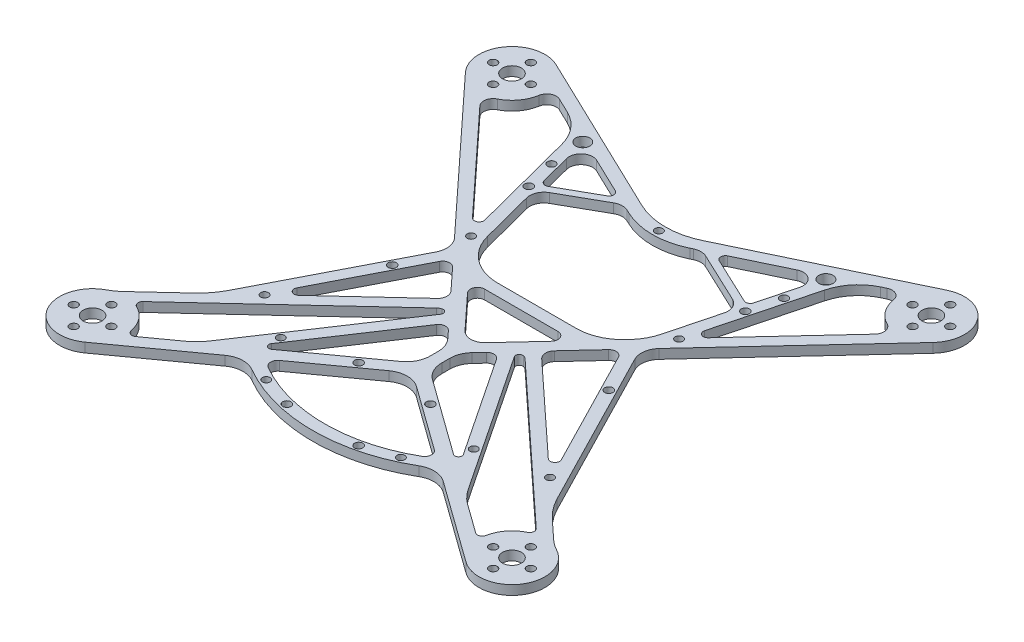
SolidWorks part; units mm, degrees
material "Thornel Mat VMA"
ref_plane "前视基准面" through (0, 0, 0) normal (0, 0, 1) x (1, 0, 0)
ref_plane "上视基准面" through (0, 0, 0) normal (0, 1, 0) x (1, 0, 0)
ref_plane "右视基准面" through (0, 0, 0) normal (1, 0, 0) x (0, 0, -1)
sketch "草图1" plane through (0, 0, 0) normal (0, 1, 0) x (1, 0, 0)
  line L0 (0, 0) -> (89.0955, 89.0955) construction
  line L1 (0, 0) -> (126, 0) construction
  line L2 (0, 0) -> (0, 126) construction
  line L3 (89.0955, 154.5955) -> (-89.0955, 154.5955)
  line L4 (154.5955, -89.0955) -> (154.5955, 89.0955)
  line L5 (-89.0955, -154.5955) -> (89.0955, -154.5955)
  line L6 (-154.5955, 89.0955) -> (-154.5955, -89.0955)
  line L7 (89.0955, 89.0955) -> (81.0955, 89.0955) construction
  circle A0 centre (0, 0) radius 126
  circle A1 centre (89.0955, 89.0955) radius 65.5
  circle A2 centre (89.0955, -89.0955) radius 65.5
  circle A3 centre (-89.0955, -89.0955) radius 65.5
  circle A4 centre (-89.0955, 89.0955) radius 65.5
  circle A5 centre (89.0955, 89.0955) radius 8 construction
  circle A6 centre (81.0955, 89.0955) radius 1.7
  circle A7 centre (89.0955, 97.0955) radius 1.7
  circle A8 centre (97.0955, 89.0955) radius 1.7
  circle A9 centre (89.0955, 81.0955) radius 1.7
  circle A10 centre (97.0955, -89.0955) radius 1.7
  circle A11 centre (89.0955, -89.0955) radius 8 construction
  circle A12 centre (89.0955, -97.0955) radius 1.7
  circle A13 centre (81.0955, -89.0955) radius 1.7
  circle A14 centre (89.0955, -81.0955) radius 1.7
  circle A15 centre (-89.0955, -97.0955) radius 1.7
  circle A16 centre (-89.0955, -89.0955) radius 8 construction
  circle A17 centre (-97.0955, -89.0955) radius 1.7
  circle A18 centre (-89.0955, -81.0955) radius 1.7
  circle A19 centre (-81.0955, -89.0955) radius 1.7
  circle A20 centre (-97.0955, 89.0955) radius 1.7
  circle A21 centre (-89.0955, 89.0955) radius 8 construction
  circle A22 centre (-89.0955, 97.0955) radius 1.7
  circle A23 centre (-81.0955, 89.0955) radius 1.7
  circle A24 centre (-89.0955, 81.0955) radius 1.7
  circle A25 centre (89.0955, 89.0955) radius 4
  circle A26 centre (89.0955, -89.0955) radius 4
  circle A27 centre (-89.0955, -89.0955) radius 4
  circle A28 centre (-89.0955, 89.0955) radius 4
  point P16 (0, 0)
  point P24 (0, 0)
  point P35 (89.0955, 89.0955)
  point P66 (0, 0)
  point P74 (0, 0)
  dimension "D1" = 252
  dimension "D3" = 131
  dimension "D6" = 3.4
  dimension "D7" = 16
  dimension "D10" = 8
  dimension "D2" = 45
  dimension "D4" = 4
  dimension "D5" = 4
  dimension "D8" = 4
  dimension "D9" = 4
  dimension "D11" = 4
extrude "凸台-拉伸1" add sketch "草图1" along normal blind 4 contours A4 A0 A3 A2 A1 | A0 A1 A9 A6 | A0 A1 A8 A7 | A2 L4 A1 A0 | A0 A2 A14 A13 | A2 A0 A12 A10 | A3 L5 A2 A0 | A0 A3 A19 A18 | A3 A0 A17 A15 | A4 L6 A3 A0 | A0 A4 A22 A20 | A0 A4 A24 A23 | A4 A0 A1 L3 region at (0, 0, -141.657) region at (106.5116, 0, -106.5116) region at (-106.5116, 0, -106.5116) region at (141.657, 0, 0) region at (0, 0, 0) region at (67.2963, 0, -67.2963) region at (-141.657, 0, 0) region at (-67.2963, 0, -67.2963) region at (106.5116, 0, 106.5116) region at (-106.5116, 0, 106.5116) region at (0, 0, 141.657) region at (67.2963, 0, 67.2963) region at (-67.2963, 0, 67.2963)
sketch "草图2" plane through (0, 4, 0) normal (0, 1, 0) x (1, 0, 0)
  circle A0 centre (-89.0955, 89.0955) radius 72
  circle A1 centre (-89.0955, 89.0955) radius 74
  circle A2 centre (89.0955, 89.0955) radius 74
  circle A3 centre (89.0955, 89.0955) radius 72
  circle A4 centre (89.0955, -89.0955) radius 74
  circle A5 centre (89.0955, -89.0955) radius 72
  circle A6 centre (-89.0955, -89.0955) radius 74
  circle A7 centre (-89.0955, -89.0955) radius 72
  point P20 (0, 0)
  dimension "D1" = 144
  dimension "D2" = 2
  dimension "D3" = 4
extrude "凸台-拉伸2" [suppressed] add sketch "草图2" along normal blind 25 separate body
sketch "草图5" plane through (0, 0, 0) normal (0, -1, 0) x (1, 0, 0)
  line L1 (-15.25, -15.25) -> (15.25, -15.25) construction
  line L2 (-15.25, -15.25) -> (-15.25, 15.25) construction
  line L3 (-15.25, 15.25) -> (15.25, 15.25) construction
  line L4 (15.25, -15.25) -> (15.25, 15.25) construction
  line L5 (-15.25, -15.25) -> (15.25, 15.25) construction
  line L6 (-15.25, 15.25) -> (15.25, -15.25) construction
  circle A0 centre (15.25, 15.25) radius 1.75
  circle A1 centre (-15.25, 15.25) radius 1.75
  circle A2 centre (-15.25, -15.25) radius 1.75
  circle A3 centre (15.25, -15.25) radius 1.75
  point P0 (0, 0)
  dimension "D2" = 3.5
  dimension "D1" = 30.5
extrude "切除-拉伸2" [suppressed] cut sketch "草图5" against normal through all
sketch "草图3" plane through (0, 0, 0) normal (0, -1, 0) x (1, 0, 0)
  line L0 (-78.4912, 99.7044) -> (0, 21.2485)
  line L1 (-89.0955, -89.0955) -> (89.0955, -89.0955) construction
  line L2 (-89.0955, -89.0955) -> (-89.0955, 89.0955) construction
  line L7 (-89.0955, 89.0955) -> (89.0955, 89.0955) construction
  line L8 (89.0955, -89.0955) -> (89.0955, 89.0955) construction
  line L9 (-89.0955, -89.0955) -> (89.0955, 89.0955) construction
  line L10 (-89.0955, 89.0955) -> (89.0955, -89.0955) construction
  line L11 (0, 21.2485) -> (78.4912, 99.7044)
  line L12 (0, 0) -> (0, 165.7353) construction
  line L13 (21.2485, 0) -> (99.7044, -78.4912)
  line L14 (99.7044, 78.4912) -> (21.2485, 0)
  line L15 (0, -21.2485) -> (-78.4912, -99.7044)
  line L16 (78.4912, -99.7044) -> (0, -21.2485)
  line L17 (-21.2485, 0) -> (-99.7044, 78.4912)
  line L18 (-99.7044, -78.4912) -> (-21.2485, 0)
  circle A4 centre (0, 0) radius 126 construction
  circle A5 centre (-89.0955, 89.0955) radius 15
  circle A6 centre (89.0955, 89.0955) radius 15
  circle A7 centre (89.0955, -89.0955) radius 15
  circle A8 centre (-89.0955, -89.0955) radius 15
  circle A9 centre (0, 0) radius 131
  circle A10 centre (0, 0) radius 121
  point P31 (0, 0)
  line M3 (-154.5955, 89.0955) -> (-154.5955, -89.0955)
  arc M4 (-154.5955, -89.0955) -> (-89.0955, -154.5955) centre (-89.0955, -89.0955) ccw
  line M5 (-89.0955, -154.5955) -> (89.0955, -154.5955)
  arc M6 (89.0955, -154.5955) -> (154.5955, -89.0955) centre (89.0955, -89.0955) ccw
  line M7 (154.5955, -89.0955) -> (154.5955, 89.0955)
  arc M8 (154.5955, 89.0955) -> (89.0955, 154.5955) centre (89.0955, 89.0955) ccw
  line M9 (89.0955, 154.5955) -> (-89.0955, 154.5955)
  arc M10 (-89.0955, 154.5955) -> (-154.5955, 89.0955) centre (-89.0955, 89.0955) ccw
  dimension "D2" = 30
  dimension "D1" = 252
  dimension "D4" = 5
  dimension "D3" = 5
  dimension "D5" = 4
extrude "切除-拉伸1" [suppressed] cut sketch "草图3" against normal through all contours A10 L17 A5 A9 A8 L18 | L17 A10 L18 | A9 A7 A8 A5 A6 M10 M3 M4 M5 M6 M7 M8 M9 | L11 A10 L0 | A10 L11 A6 A9 A5 L0 | L13 A10 L14 | A10 L13 A7 A9 A6 L14 | A10 L15 A8 A9 A7 L16 | L15 A10 L16
sketch "草图6" plane through (0, 0, 0) normal (0, -1, 0) x (1, 0, 0)
  line L0 (-198.0374, 0) -> (198.0374, 0) construction
  line L1 (0, -184.6466) -> (0, 184.6466) construction
  line L2 (89.0955, 103.0955) -> (-89.0955, 103.0955)
  line L3 (103.0955, 89.0955) -> (103.0955, -89.0955)
  line L4 (89.0955, -103.0955) -> (-89.0955, -103.0955)
  line L5 (-103.0955, 89.0955) -> (-103.0955, -89.0955)
  line L10 (-154.5955, 89.0955) -> (-154.5955, -89.0955)
  line L11 (-89.0955, -154.5955) -> (89.0955, -154.5955)
  line L12 (154.5955, -89.0955) -> (154.5955, 89.0955)
  line L13 (89.0955, 154.5955) -> (-89.0955, 154.5955)
  line L14 (-154.5955, 89.0955) -> (-154.5955, -89.0955)
  line L15 (-89.0955, -154.5955) -> (89.0955, -154.5955)
  line L16 (154.5955, -89.0955) -> (154.5955, 89.0955)
  line L17 (89.0955, 154.5955) -> (-89.0955, 154.5955)
  circle A0 centre (89.0955, 89.0955) radius 14
  circle A1 centre (89.0955, -89.0955) radius 14
  circle A2 centre (-89.0955, -89.0955) radius 14
  circle A3 centre (-89.0955, 89.0955) radius 14
  arc A8 (-154.5955, -89.0955) -> (-89.0955, -154.5955) centre (-89.0955, -89.0955) ccw
  arc A9 (89.0955, -154.5955) -> (154.5955, -89.0955) centre (89.0955, -89.0955) ccw
  arc A10 (154.5955, 89.0955) -> (89.0955, 154.5955) centre (89.0955, 89.0955) ccw
  arc A11 (-89.0955, 154.5955) -> (-154.5955, 89.0955) centre (-89.0955, 89.0955) ccw
  arc A12 (-154.5955, -89.0955) -> (-89.0955, -154.5955) centre (-89.0955, -89.0955) ccw
  arc A13 (89.0955, -154.5955) -> (154.5955, -89.0955) centre (89.0955, -89.0955) ccw
  arc A14 (154.5955, 89.0955) -> (89.0955, 154.5955) centre (89.0955, 89.0955) ccw
  arc A15 (-89.0955, 154.5955) -> (-154.5955, 89.0955) centre (-89.0955, 89.0955) ccw
  point P7 (0, 0)
  point P11 (0, 0)
  point P20 (0, 0)
  line M5 (-154.5955, 89.0955) -> (-154.5955, -89.0955)
  arc M6 (-154.5955, -89.0955) -> (-89.0955, -154.5955) centre (-89.0955, -89.0955) ccw
  line M7 (-89.0955, -154.5955) -> (89.0955, -154.5955)
  arc M8 (89.0955, -154.5955) -> (154.5955, -89.0955) centre (89.0955, -89.0955) ccw
  line M9 (154.5955, -89.0955) -> (154.5955, 89.0955)
  arc M10 (154.5955, 89.0955) -> (89.0955, 154.5955) centre (89.0955, 89.0955) ccw
  line M11 (89.0955, 154.5955) -> (-89.0955, 154.5955)
  arc M12 (-89.0955, 154.5955) -> (-154.5955, 89.0955) centre (-89.0955, 89.0955) ccw
  dimension "D1" = 28
  dimension "D3" = 0
  dimension "D2" = 4
extrude "切除-拉伸3" cut sketch "草图6" against normal blind 10 contours A3 L2 A0 L3 A1 L4 A2 L5 M12 M5 M6 M7 M8 M9 M10 M11 region at (-132.319, 0, 132.319)
sketch "草图8" plane through (0, 4, 0) normal (0, 1, 0) x (1, 0, 0)
  line L0 (-127.7176, 0) -> (127.7176, 0) construction
  line L1 (0, -110.9054) -> (0, 110.9054) construction
  line L2 (-28.9, 35.15) -> (28.9, 35.15) construction
  line L4 (-31.72, 13.9302) -> (31.72, 13.9302)
  line L5 (-31.72, 13.9302) -> (-31.72, 56.3698)
  line L6 (-28.9, 54.35) -> (-28.9, 15.95)
  line L7 (-28.9, 15.95) -> (28.9, 15.95)
  line L8 (28.9, 15.95) -> (28.9, 54.35)
  line L9 (28.9, 54.35) -> (-28.9, 54.35)
  line L10 (-28.9, 54.35) -> (-28.9, 15.95) construction
  line L11 (-28.9, 15.95) -> (28.9, 15.95) construction
  line L12 (28.9, 15.95) -> (28.9, 54.35) construction
  line L13 (28.9, 54.35) -> (-28.9, 54.35) construction
  line L14 (-31.72, 56.3698) -> (31.72, 56.3698)
  line L15 (31.72, 13.9302) -> (31.72, 56.3698)
  line L16 (-31.72, 13.9302) -> (31.72, 56.3698) construction
  line L17 (-31.72, 56.3698) -> (31.72, 13.9302) construction
  point P4 (0, 0)
  point P8 (0, 0)
  point P14 (0, 35.15)
  dimension "D1" = 0
extrude "切除-拉伸4" cut sketch "草图8" against normal blind 10
sketch "草图9" plane through (0, 4, 0) normal (0, 1, 0) x (1, 0, 0)
  circle A0 centre (-15.25, -49.9) radius 1.75
  circle A1 centre (15.25, -49.9) radius 1.75
  circle A2 centre (15.25, -80.4) radius 1.75
  circle A3 centre (-15.25, -80.4) radius 1.75
  dimension "D1" = 3.5
extrude "切除-拉伸5" cut sketch "草图9" against normal blind 10
sketch "草图10" plane through (0, 0, 0) normal (0, -1, 0) x (1, 0, 0)
  circle A0 centre (-44, -51.14) radius 1.75
  circle A1 centre (48, -51.14) radius 1.75
  circle A2 centre (48, 6.86) radius 1.75
  circle A3 centre (-44, 6.86) radius 1.75
  dimension "D1" = 3.5
extrude "切除-拉伸6" cut sketch "草图10" against normal blind 10
sketch "草图11" plane through (0, 0, 0) normal (0, -1, 0) x (1, 0, 0)
  line L0 (0, 132.3429) -> (0, -132.3429) construction
  line L1 (-99.3649, -79.5803) -> (-19.273, 6.86)
  line L2 (-19.273, 6.86) -> (-93.793, 75.9071)
  line L3 (-44, 6.86) -> (-135.4224, 6.86) construction
  line L4 (-35.1821, -10.3101) -> (-66.4476, 50.57) construction
  line L5 (-88.4087, -75.1123) -> (0, 20.304)
  line L6 (-83.0441, -101.7201) -> (0, -61.9145)
  line L7 (0, -56.3698) -> (-75.535, -92.576)
  line L8 (-103.0955, 89.0955) -> (-103.0955, -89.0955)
  line L9 (89.0955, 103.0955) -> (-89.0955, 103.0955)
  line L10 (103.0955, -89.0955) -> (103.0955, 89.0955)
  line L11 (-89.0955, -103.0955) -> (89.0955, -103.0955)
  line L12 (-103.0955, 89.0955) -> (-103.0955, -89.0955)
  line L13 (89.0955, 103.0955) -> (-89.0955, 103.0955)
  line L14 (103.0955, -89.0955) -> (103.0955, 89.0955)
  line L15 (-89.0955, -103.0955) -> (89.0955, -103.0955)
  line L16 (31.72, -56.3698) -> (-31.72, -56.3698) construction
  line L17 (-35.3144, -17.8096) -> (-51.8378, -81.2172) construction
  line L18 (-31.72, -13.9302) -> (-48.8856, -79.8021)
  line L19 (-54.7901, -82.6323) -> (-38.9088, -21.6889)
  line L20 (-85.9474, 75.454) -> (-15.8747, 10.5276)
  line L21 (-15.8747, 10.5276) -> (0, 27.6607)
  line L22 (-15.25, 49.9) -> (15.25, 80.4) construction
  line L23 (-2.5, 24.9625) -> (-2.5, 43.9914)
  line L24 (-33.3739, -8.3586) -> (-61.0859, 45.602)
  line L25 (-36.9903, -12.2617) -> (-71.8093, 55.5379)
  line L26 (-32.9583, -9.1681) -> (-64.2237, 51.7121) construction
  line L27 (-37.406, -11.4522) -> (-68.6715, 49.4279) construction
  line L28 (169.5606, 0) -> (-169.5606, 0) construction
  line L29 (-80.9146, 100.4565) -> (0, 42.1912)
  line L30 (-2.5, 40.7189) -> (-75.8088, 93.5074) construction
  line L31 (2.5, 24.9625) -> (2.5, 43.9914)
  line L32 (-75.1099, 89.7316) -> (-2.5, 37.4464)
  line L33 (2.5, 40.7189) -> (75.8088, 93.5074) construction
  line L34 (15.25, 49.9) -> (-15.25, 80.4) construction
  line L35 (35.3144, -17.8096) -> (51.8378, -81.2172) construction
  line L36 (35.1821, -10.3101) -> (66.4476, 50.57) construction
  line L37 (44, 6.86) -> (135.4224, 6.86) construction
  line L38 (75.1099, 89.7316) -> (2.5, 37.4464)
  line L39 (80.9146, 100.4565) -> (0, 42.1912)
  line L40 (74.0789, 57.6408) -> (37.7557, -13.0877) construction
  line L41 (68.7171, 52.6728) -> (35.9475, -11.1362)
  line L42 (15.8747, 10.5276) -> (0, 27.6607)
  line L43 (85.9474, 75.454) -> (15.8747, 10.5276)
  line L44 (40.8796, -23.8159) -> (56.4088, -83.4082) construction
  line L45 (37.2852, -19.9366) -> (53.4565, -81.9931)
  line L46 (103.0955, 89.0955) -> (103.0955, -89.0955)
  line L47 (0, -56.3698) -> (75.535, -92.576)
  line L48 (83.0441, -101.7201) -> (0, -61.9145)
  line L49 (88.4087, -75.1123) -> (0, 20.304)
  line L50 (19.273, 6.86) -> (93.793, 75.9071)
  line L51 (99.3649, -79.5803) -> (19.273, 6.86)
  line L52 (79.4406, 62.6087) -> (39.5639, -15.0392)
  line L53 (71.855, 58.7829) -> (35.5318, -11.9456) construction
  line L54 (76.3027, 56.4987) -> (39.9796, -14.2298) construction
  line L55 (-24.7708, -6.4302) -> (24.7708, -6.4302) construction
  line L56 (-27.0872, -8.9302) -> (27.0872, -8.9302)
  line L57 (-22.4544, -3.9302) -> (22.4544, -3.9302)
  line L58 (-24.7708, -3.9302) -> (24.7708, -3.9302) construction
  line L59 (-24.7708, -8.9302) -> (24.7708, -8.9302) construction
  line L60 (-31.72, -13.9302) -> (31.72, -13.9302) construction
  line L61 (44.474, -27.6952) -> (59.361, -84.8233)
  line L62 (43.2988, -23.1854) -> (58.828, -82.7778) construction
  line L63 (38.4604, -24.4463) -> (53.9896, -84.0386) construction
  circle A0 centre (-89.0955, -89.0955) radius 14
  circle A1 centre (-89.0955, 89.0955) radius 14
  arc A2 (15.25, 80.4) -> (-38.6908, 70.0519) centre (0, 14.1321) ccw construction
  arc A3 (15.8107, 82.8363) -> (-40.8391, 71.5988) centre (0, 14.1321) ccw
  arc A4 (14.6893, 77.9637) -> (-36.5325, 68.4977) centre (0, 14.1321) ccw
  arc A5 (14.6893, 77.9637) -> (-37.2684, 67.996) centre (0, 14.1321) ccw construction
  arc A6 (-89.0955, 103.0955) -> (-103.0955, 89.0955) centre (-89.0955, 89.0955) ccw
  arc A7 (103.0955, 89.0955) -> (89.0955, 103.0955) centre (89.0955, 89.0955) ccw
  arc A8 (89.0955, -103.0955) -> (103.0955, -89.0955) centre (89.0955, -89.0955) ccw
  arc A9 (-103.0955, -89.0955) -> (-89.0955, -103.0955) centre (-89.0955, -89.0955) ccw
  arc A10 (-89.0955, 103.0955) -> (-103.0955, 89.0955) centre (-89.0955, 89.0955) ccw
  arc A11 (103.0955, 89.0955) -> (89.0955, 103.0955) centre (89.0955, 89.0955) ccw
  arc A12 (89.0955, -103.0955) -> (103.0955, -89.0955) centre (89.0955, -89.0955) ccw
  arc A13 (-103.0955, -89.0955) -> (-89.0955, -103.0955) centre (-89.0955, -89.0955) ccw
  arc A14 (15.8107, 82.8363) -> (-40.1133, 72.1077) centre (0, 14.1321) ccw construction
  arc A15 (-15.25, 80.4) -> (38.6908, 70.0519) centre (0, 14.1321) cw construction
  arc A16 (103.0955, -89.0955) -> (89.0955, -103.0955) centre (89.0955, -89.0955) cw
  arc A17 (89.0955, 103.0955) -> (103.0955, 89.0955) centre (89.0955, 89.0955) cw
  arc A18 (-14.6893, 77.9637) -> (36.5325, 68.4977) centre (0, 14.1321) cw
  arc A19 (-15.8107, 82.8363) -> (40.8391, 71.5988) centre (0, 14.1321) cw
  circle A20 centre (89.0955, 89.0955) radius 14
  circle A21 centre (89.0955, -89.0955) radius 14
  point P4 (0, 0)
  point P44 (-44, -51.14)
  point P78 (-15.25, 80.4)
  point P91 (0, 0)
  point P115 (48, -51.14)
  point P123 (44, -51.14)
  point P124 (48, 6.86)
  circle M19 centre (48, -51.14) radius 1.75
  line M25 (-31.72, -13.9302) -> (31.72, -13.9302)
  line M26 (31.72, -13.9302) -> (31.72, -56.3698)
  line M27 (31.72, -56.3698) -> (-31.72, -56.3698)
  line M28 (-31.72, -56.3698) -> (-31.72, -13.9302)
  line M50 (-103.0955, 89.0955) -> (-103.0955, -89.0955)
  line M52 (-89.0955, -103.0955) -> (89.0955, -103.0955)
  line M54 (103.0955, -89.0955) -> (103.0955, 89.0955)
  line M56 (89.0955, 103.0955) -> (-89.0955, 103.0955)
  dimension "D13" = 68
  dimension "D2" = 5
  dimension "D3" = 5
  dimension "D4" = 5
  dimension "D5" = 5
  dimension "D8" = 160
  dimension "D9" = 2.5
  dimension "D12" = 5.3113
  dimension "D18" = 5
  dimension "D1" = 0
  dimension "D6" = 2.5
  dimension "D7" = 2.5
  dimension "D10" = 2.5
  dimension "D11" = 2.5
  dimension "D14" = 2.5
  dimension "D15" = 2.5
  dimension "D16" = 2.5
  dimension "D17" = 2.5
  dimension "D19" = 2.5
  dimension "D20" = 2.5
extrude "切除-拉伸7" cut sketch "草图11" against normal blind 10 contours L5 L57 L49 | L56 L5 L49 M25 | L18 L7 M28 M27 | L47 M27 M26 | A21 L48 L6 A0 M52 | L47 A21 L49 M19 | L51 A21 A20 L50 L52 M54 | L51 L41 L50 | L43 A20 L38 L31 L42 | A18 A4 L29 L39 | L39 A20 A1 L29 A3 A19 M56 | A1 L20 L21 L23 L32 | L24 L1 L2 | A1 A0 L1 L25 L2 M50 | A0 L7 L19 L5 region at (-80.1062, 0, 0.3007) region at (-61.8775, 0, -63.0239) region at (-37.9109, 0, 14.7011) region at (0, 0, -89.3741) region at (-32.1021, 0, -57.1783) region at (0, 0, -11.4959) region at (0, 0, 91.9564) region at (-40.0507, 0, 49.3053) region at (34.865, 0, -55.0414) region at (81.2608, 0, -0.8208) region at (0, 0, 4.1478) region at (64.7895, 0, -65.0788) region at (40.0507, 0, 49.3053) region at (0, 0, 64.567) region at (41.3125, 0, 16.1322)
fillet "圆角1" radius 30 2 edges at (0, 2, -56.3698) (0, 2, -61.9145)
fillet "圆角2" radius 4 4 edges at (75.535, 2, -92.576) (88.4087, 2, -75.1123) (-75.535, 2, -92.576) (-88.4087, 2, -75.1123)
fillet "圆角3" radius 2 4 edges at (-75.1099, 2, 89.7316) (-85.9474, 2, 75.454) (75.1099, 2, 89.7316) (85.9474, 2, 75.454)
fillet "圆角4" radius 20 2 edges at (-54.7901, 2, -82.6323) (59.361, 2, -84.8233)
fillet "圆角5" radius 20 2 edges at (27.0872, 2, -8.9302) (-27.0872, 2, -8.9302)
fillet "圆角6" radius 20 2 edges at (-31.72, 2, -13.9302) (37.2852, 2, -19.9366)
fillet "圆角7" radius 2 2 edges at (-38.9088, 2, -21.6889) (44.474, 2, -27.6952)
fillet "圆角8" radius 3 2 edges at (22.4544, 2, -3.9302) (-22.4544, 2, -3.9302)
fillet "圆角9" radius 6 1 edges at (0, 2, 20.304)
fillet "圆角10" radius 2 2 edges at (68.7171, 2, 52.6728) (-61.0859, 2, 45.602)
fillet "圆角11" radius 4 2 edges at (19.273, 2, 6.86) (-19.273, 2, 6.86)
fillet "圆角12" radius 8 2 edges at (39.5639, 2, -15.0392) (-36.9903, 2, -12.2617)
fillet "圆角13" radius 30 2 edges at (79.4406, 2, 62.6087) (-71.8093, 2, 55.5379)
fillet "圆角14" radius 3 2 edges at (35.9475, 2, -11.1362) (-33.3739, 2, -8.3586)
fillet "圆角15" radius 10 5 edges at (0, 2, 42.1912) (-2.5, 2, 24.9625) (2.5, 2, 24.9625) (2.5, 2, 37.4464) (-2.5, 2, 37.4464)
fillet "圆角16" radius 4 2 edges at (-15.8747, 2, 10.5276) (15.8747, 2, 10.5276)
fillet "圆角17" radius 10 2 edges at (40.8391, 2, 71.5988) (-40.8391, 2, 71.5988)
fillet "圆角18" radius 3 2 edges at (36.5325, 2, 68.4977) (-36.5325, 2, 68.4977)
fillet "圆角19" radius 5 2 edges at (53.4565, 2, -81.9931) (-48.8856, 2, -79.8021)
sketch "草图12" plane through (0, 4, 0) normal (0, 1, 0) x (1, 0, 0)
  line L0 (0, 0) -> (0, 104.7787) construction
  circle A0 centre (-48.813, 78.888) radius 3
  circle A1 centre (53.365, 80.0085) radius 3
  dimension "D1" = 6
  dimension "D2" = 6
extrude "切除-拉伸8" cut sketch "草图12" against normal up to next
sketch "草图13" plane through (0, 4, 0) normal (0, 1, 0) x (1, 0, 0)
  line L0 (0, 0) -> (0, 105.1659) construction
  line L1 (-44, 51.14) -> (-18.812, 65.3869) construction
  line L2 (-39.1687, 75.1445) -> (-12.9672, 62.5853) construction
  line L3 (-41.357, 50.9116) -> (-17.1628, 64.5964)
  line L4 (-42.1398, 53.9155) -> (-20.4612, 66.1774)
  line L5 (-20.4612, 66.1774) -> (-17.1628, 64.5964)
  line L6 (-43.2615, 49.8344) -> (-18.0735, 64.0813) construction
  line L7 (-44.7385, 52.4456) -> (-19.5505, 66.6925) construction
  line L8 (-46.1683, 69.3749) -> (-34.3146, 23.8869) construction
  line L9 (-42.1398, 53.9155) -> (-41.357, 50.9116)
  line L10 (48, 51.14) -> (18.3136, 65.148) construction
  line L11 (43.7397, 77.3355) -> (12.9672, 62.5853) construction
  line L12 (46.0843, 53.7026) -> (20.0573, 65.9838)
  line L13 (45.3145, 50.7486) -> (16.5698, 64.3122)
  line L14 (50.7393, 71.5659) -> (38.5525, 24.7998) construction
  line L15 (46.0843, 53.7026) -> (45.3145, 50.7486)
  line L16 (20.0573, 65.9838) -> (16.5698, 64.3122)
  line L17 (48.6401, 52.4966) -> (18.9537, 66.5046) construction
  line L18 (47.3599, 49.7834) -> (17.6734, 63.7914) construction
  dimension "D1" = 1.5
  dimension "D2" = 1.5
  dimension "D3" = 1.5
  dimension "D4" = 1.5
extrude "凸台-拉伸3" add sketch "草图13" against normal up to surface (4 mm away) up to face at (-48.813, 0, -75.888)
fillet "圆角20" radius 2 4 edges at (-42.1398, 2, -53.9155) (-20.4612, 2, -66.1774) (20.0573, 2, -65.9838) (46.0843, 2, -53.7026)
fillet "圆角21" radius 6 4 edges at (-41.357, 2, -50.9116) (-17.1628, 2, -64.5964) (16.5698, 2, -64.3122) (45.3145, 2, -50.7486)
sketch "草图14" plane through (0, 0, 0) normal (0, -1, 0) x (1, 0, 0)
  line L0 (-51.1329, 72.4661) -> (-12.3959, 14.2822) construction
  line L1 (-72.2232, 87.6529) -> (-6.6565, 40.4395) construction
  line L2 (-13.1561, 13.4618) -> (-5.1647, 22.0866) construction
  line L3 (-13.1561, 13.4618) -> (-5.1647, 22.0866)
  line L4 (-72.2232, 87.6529) -> (-6.6565, 40.4395)
  line L5 (-56.902, 76.6204) -> (-14.2862, 12.6103)
  line L6 (-45.3637, 68.3119) -> (-10.6482, 16.1684)
  line L7 (-49.0519, 73.8516) -> (-10.3149, 15.6677) construction
  line L8 (-53.2139, 71.0807) -> (-14.4769, 12.8968) construction
  line L9 (0, 0) -> (0, 114.9846) construction
  line L10 (51.1329, 72.4661) -> (12.3959, 14.2822) construction
  line L11 (45.3637, 68.3119) -> (10.6482, 16.1684)
  line L12 (56.902, 76.6204) -> (14.2862, 12.6103)
  line L13 (72.2232, 87.6529) -> (6.6565, 40.4395)
  line L14 (13.1561, 13.4618) -> (5.1647, 22.0866)
  arc A0 (-18.8088, 13.2463) -> (-13.1561, 13.4618) centre (-16.0902, 16.1804) ccw construction
  arc A1 (-18.8088, 13.2463) -> (-13.1561, 13.4618) centre (-16.0902, 16.1804) ccw
  arc A2 (18.8088, 13.2463) -> (13.1561, 13.4618) centre (16.0902, 16.1804) cw
  dimension "D1" = 2.5
  dimension "D2" = 2.5
extrude "凸台-拉伸4" add sketch "草图14" against normal up to surface (4 mm away) contours L5 A1 L3 L6 L4 | A2 L12 L13 L11 L14 region at (-31.9007, 0, 43.4242) region at (31.9007, 0, 43.4242) up to face at (38.9653, 4, -65.5392)
fillet "圆角22" radius 1.5 2 edges at (-14.2862, 2, 12.6103) (14.2862, 2, 12.6103)
fillet "圆角23" radius 1.5 2 edges at (45.3637, 2, 68.3119) (-45.3637, 2, 68.3119)
fillet "圆角24" radius 3 2 edges at (-10.6482, 2, 16.1684) (10.6482, 2, 16.1684)
fillet "圆角25" radius 20 2 edges at (-56.902, 2, 76.6204) (56.902, 2, 76.6204)
sketch "草图15" plane through (0, 0, 0) normal (0, -1, 0) x (1, 0, 0)
  circle A0 centre (-40.99, 57.2312) radius 1.65
  circle A1 centre (40.99, 57.2312) radius 1.65
  dimension "D1" = 3.3
extrude "切除-拉伸9" cut sketch "草图15" against normal up to next
sketch "草图16" plane through (0, 0, 0) normal (0, -1, 0) x (1, 0, 0)
  line L0 (0, -59.6381) -> (0, -65.1828) construction
  arc A0 (12.9672, -62.5853) -> (-12.9672, -62.5853) centre (0, -89.6381) ccw construction
  arc A1 (12.9672, -68.1301) -> (-12.9672, -68.1301) centre (0, -95.1828) ccw construction
  circle A2 centre (0, -62.4104) radius 1.65
  dimension "D1" = 3.3
extrude "切除-拉伸10" cut sketch "草图16" against normal through all
sketch "草图17" plane through (0, 4, 0) normal (0, 1, 0) x (1, 0, 0)
  line L0 (-44.9774, 64.8048) -> (-49.8159, 63.544) construction
  line L1 (-46.1683, 69.3749) -> (-42.7957, 56.4326) construction
  line L2 (-40.9158, 29.3908) -> (-52.4499, 73.6519) construction
  line L3 (48.9774, 64.8048) -> (53.8159, 63.544) construction
  line L4 (50.7393, 71.5659) -> (46.6924, 56.036) construction
  line L5 (57.0208, 75.8429) -> (46.481, 35.3971) construction
  circle A0 centre (-47.3966, 64.1744) radius 1.7
  circle A1 centre (51.3966, 64.1744) radius 1.7
  dimension "D1" = 3.4
extrude "切除-拉伸11" cut sketch "草图17" against normal through all
sketch "草图18" plane through (0, 4, 0) normal (0, 1, 0) x (1, 0, 0)
  line L0 (-27.6691, -73.501) -> (-29.5512, -78.1397) construction
  line L1 (0, 0) -> (0, -122.9077) construction
  circle A0 centre (44.1, 26.89) radius 1.65
  circle A1 centre (-37.9298, 20.5529) radius 1.65
  circle A2 centre (-60.2014, -44.9335) radius 1.65
  circle A3 centre (67.6329, -51.4873) radius 1.65
  arc A4 (-32.6432, -70.9182) -> (32.6432, -70.9182) centre (0, -14.1321) ccw construction
  arc A5 (-35.4856, -75.0503) -> (35.4856, -75.0503) centre (0, -14.1321) ccw construction
  circle A6 centre (-28.6101, -75.8204) radius 1.65
  circle A7 centre (28.6101, -75.8204) radius 1.65
  dimension "D1" = 3.3
  dimension "D2" = 3.3
  dimension "D3" = 3.3
extrude "切除-拉伸12" cut sketch "草图18" against normal through all
fillet "圆角26" radius 20 2 edges at (-93.793, 2, 75.9071) (93.793, 2, 75.9071)
